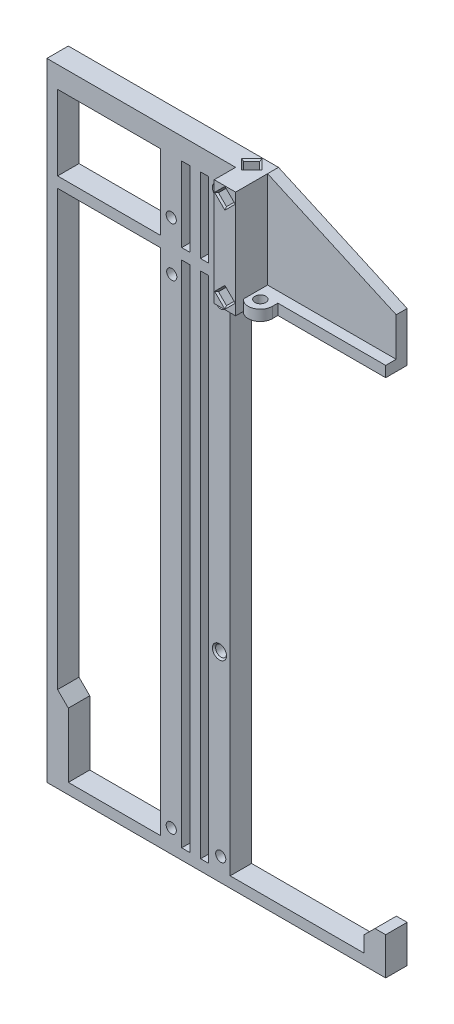
SolidWorks part; units mm, degrees
ref_plane "Front Plane" through (0, 0, 0) normal (0, 0, 1) x (1, 0, 0)
ref_plane "Top Plane" through (0, 0, 0) normal (0, 1, 0) x (1, 0, 0)
ref_plane "Right Plane" through (0, 0, 0) normal (1, 0, 0) x (0, 0, -1)
sketch "matx screw pattern" plane through (0, 0, 0) normal (0, 0, 1) x (1, 0, 0)
  line L1 (-121.92, 121.92) -> (121.92, 121.92) construction
  line L2 (-121.92, 121.92) -> (-121.92, -121.92) construction
  line L3 (-121.92, -121.92) -> (121.92, -121.92) construction
  line L4 (121.92, 121.92) -> (121.92, -121.92) construction
  point P4 (0, 121.92)
  point P6 (121.92, 0)
  point P7 (-111.76, -87.63)
  point P8 (-111.76, -41.91)
  point P9 (-88.9, 115.57)
  point P10 (43.18, -41.91)
  point P11 (43.18, -87.63)
  point P12 (43.18, -107.95)
  point P13 (115.57, -41.91)
  point P14 (115.57, 115.57)
  point P15 (43.18, 115.57)
  dimension "D1" = 243.84
  dimension "D2" = 10.16
  dimension "D3" = 22.86
  dimension "D4" = 227.33
  dimension "D5" = 154.94
  dimension "D6" = 203.2
  dimension "D7" = 45.72
  dimension "D8" = 20.32
  dimension "D9" = 34.29
sketch "Sketch1" plane through (0, 0, 0) normal (0, 0, 1) x (1, 0, 0)
  line L11 (47.4133, 127) -> (130.429, 127)
  line L12 (119.8033, 118.5333) -> (119.8033, 88.9)
  line L13 (181.229, -120.65) -> (47.4133, -120.65)
  line L14 (55.88, -116.4167) -> (55.88, -120.65) construction
  line L15 (55.88, -116.4167) -> (55.88, -91.0167)
  line L16 (51.6467, 118.5333) -> (92.1956, 118.5333)
  line L17 (51.6467, 118.5333) -> (51.6467, 88.9)
  line L18 (55.88, -116.4167) -> (92.1956, -116.4167)
  line L19 (111.3367, 118.5333) -> (111.3367, 88.9)
  line L20 (55.88, -91.0167) -> (51.6467, -86.7833)
  line L21 (119.8033, 118.5333) -> (121.9623, 118.5333)
  line L22 (121.9623, 118.5333) -> (121.9623, 88.9)
  line L26 (130.429, 127) -> (130.429, 88.9)
  line L27 (119.8033, -116.4167) -> (172.7623, -116.4167)
  line L29 (55.88, -116.4167) -> (47.4133, -116.4167) construction
  line L30 (47.4133, -120.65) -> (47.4133, 127)
  line L31 (172.7623, -116.4167) -> (172.7623, -110.0667)
  line L32 (172.7623, -110.0667) -> (176.9957, -105.8333)
  line L33 (92.1956, 118.5333) -> (92.1956, 88.9)
  line L34 (51.6467, 84.6667) -> (92.1956, 84.6667)
  line L35 (100.6623, -116.4167) -> (103.8828, -116.4167)
  line L36 (100.6623, 118.5333) -> (100.6623, 88.9)
  line L37 (100.6623, 118.5333) -> (103.8828, 118.5333)
  line L38 (100.6623, 84.6667) -> (103.8828, 84.6667)
  line L40 (119.8033, 84.6667) -> (181.229, 84.6667)
  line L41 (51.6467, 88.9) -> (92.1956, 88.9)
  line L42 (100.6623, 88.9) -> (103.8828, 88.9)
  line L43 (119.8033, 88.9) -> (121.9623, 88.9)
  line L44 (130.429, 88.9) -> (181.229, 88.9)
  line L45 (92.1956, -116.4167) -> (100.6623, -116.4167) construction
  line L46 (51.6467, 84.6667) -> (51.6467, -86.7833)
  line L47 (92.1956, 84.6667) -> (92.1956, -116.4167)
  line L48 (100.6623, 84.6667) -> (100.6623, -116.4167)
  line L49 (111.3367, 84.6667) -> (111.3367, -116.4167)
  line L50 (119.8033, 84.6667) -> (119.8033, -116.4167)
  line L54 (111.3367, -116.4167) -> (119.8033, -116.4167) construction
  line L55 (51.6467, 118.5333) -> (51.6467, 127) construction
  line L56 (172.7623, -116.4167) -> (181.229, -116.4167) construction
  line L57 (51.6467, -86.7833) -> (47.4133, -86.7833) construction
  line L58 (176.9957, -105.8333) -> (181.229, -105.8333)
  line L59 (51.6467, 88.9) -> (51.6467, 84.6667) construction
  line L60 (-121.92, 121.92) -> (121.92, 121.92) construction
  line L61 (121.9623, 88.9) -> (130.429, 88.9) construction
  line L62 (181.229, -105.8333) -> (181.229, -120.65)
  line L63 (103.8828, 118.5333) -> (103.8828, 88.9)
  line L64 (108.1161, 118.5333) -> (108.1161, 88.9)
  line L65 (108.1161, -116.4167) -> (111.3367, -116.4167)
  line L66 (108.1161, 88.9) -> (111.3367, 88.9)
  line L67 (108.1161, 84.6667) -> (111.3367, 84.6667)
  line L68 (103.8828, 84.6667) -> (103.8828, -116.4167)
  line L69 (108.1161, 84.6667) -> (108.1161, -116.4167)
  line L70 (108.1161, 118.5333) -> (111.3367, 118.5333)
  line L71 (103.8828, -116.4167) -> (108.1161, -116.4167) construction
  line L72 (181.229, 88.9) -> (181.229, 84.6667)
  point P0 (115.57, -116.4167)
  dimension "D2" = 4.2333
  dimension "D3" = 38.1
  dimension "D4" = 8.4667
  dimension "D5" = 4.2333
  dimension "D6" = 5.08
  dimension "D7" = 6.35
  dimension "D8" = 25.4
  dimension "D9" = 50.8
  dimension "D10" = 45
  dimension "D11" = 247.65
  dimension "D12" = 133.8157
  dimension "D13" = 40.549
extrude "Boss-Extrude1" add sketch "Sketch1" against normal blind 8.4667 from offset 9.525 offset against normal yes
sketch "Sketch9" plane through (0, 0, -17.9917) normal (0, 0, 1) x (1, 0, 0)
  line L3 (181.229, 88.9) -> (130.429, 88.9)
  line L4 (130.429, 127) -> (130.429, 88.9)
  line L7 (130.429, 127) -> (181.229, 104.14)
  line L9 (181.229, 104.14) -> (181.229, 88.9)
  dimension "D1" = 38.1
  dimension "D2" = 15.24
extrude "Boss-Extrude2" add sketch "Sketch9" along normal blind 4.318
sketch "Sketch16" plane through (0, 0, -9.525) normal (0, 0, 1) x (1, 0, 0)
  line L0 (119.8033, 84.6667) -> (181.229, 84.6667) construction
  line L1 (130.429, 127) -> (121.9623, 127)
  line L2 (130.429, 127) -> (130.429, 84.6667)
  line L3 (130.429, 84.6667) -> (121.9623, 84.6667)
  line L4 (121.9623, 127) -> (121.9623, 84.6667)
  line L5 (121.9623, 88.9) -> (121.9623, 118.5333) construction
extrude "Boss-Extrude3" add sketch "Sketch16" along normal blind 8.4667
sketch "Sketch18" plane through (0, 84.6667, 0) normal (0, -1, 0) x (-1, 0, 0)
  line L0 (-138.6515, 7.3467) -> (-138.6515, 9.525)
  line L1 (-47.4133, 9.525) -> (-181.229, 9.525) construction
  line L2 (-129.1265, 7.3467) -> (-129.1265, 9.525)
  line L3 (-138.6515, 9.525) -> (-129.1265, 9.525)
  arc A0 (-138.6515, 7.3467) -> (-129.1265, 7.3467) centre (-133.889, 7.3467) ccw
  point P1 (-133.889, 7.3467)
  point P8 (-133.889, 7.3467)
  dimension "D1" = 9.525
extrude "Boss-Extrude4" add sketch "Sketch18" against normal up to surface (4.2333 mm away) up to face at (155.829, 88.9, -11.5993)
sketch "Sketch21" plane through (0, 88.9, 0) normal (0, 1, 0) x (1, 0, 0)
  arc A0 (130.429, 4.0741) -> (138.6515, 7.3467) centre (133.889, 7.3467) ccw construction
  point P0 (133.889, 7.3467)
hole_wizard "#18 (0.1695) Diameter Hole3" positions "Sketch21" profile "Sketch22" hole size "#18" standard "ANSI Inch" end condition up to next
sketch "Sketch22" plane through (133.889, 88.9, -7.3467) normal (1, 0, 0) x (0, 0, 1)
  line L0 (0, 0) -> (0, 4.2333)
  line L1 (0, 4.2333) -> (2.1526, 4.2333)
  line L2 (2.1526, 4.2333) -> (2.1526, 0)
  line L5 (2.1526, 0) -> (0, 0)
  line L11 (0, -6.35) -> (0, 107.95) construction
  dimension "Thru Hole Dia." = 4.3053
  dimension "Thru Hole Depth" = 4.2333
sketch "Sketch5" plane through (0, 0, -9.525) normal (0, 0, 1) x (1, 0, 0)
  point P15 (115.57, 115.57)
  point P18 (115.57, -41.91)
hole_wizard "#18 (0.1695) Diameter Hole1" positions "Sketch5" profile "Sketch6" hole size "#18" standard "ANSI Inch" end condition through all
sketch "Sketch6" plane through (115.57, 115.57, -9.525) normal (1, 0, 0) x (0, -1, 0)
  line L0 (0, 0) -> (0, 8.4667)
  line L1 (0, 8.4667) -> (2.1526, 8.4667)
  line L2 (2.1526, 8.4667) -> (2.1526, 0.635)
  line L3 (2.1526, 0.635) -> (2.7876, 0)
  line L5 (2.7876, 0) -> (0, 0)
  line L6 (-2.1526, 0.635) -> (-2.7876, 0) construction
  line L11 (0, -6.35) -> (0, 107.95) construction
  dimension "Thru Hole Dia." = 4.3053
  dimension "Thru Hole Depth" = 8.4667
  dimension "Near C'Sink Dia." = 5.5753
  dimension "Near C'Sink Angle" = 90
sketch "Sketch2" plane through (0, -120.65, 0) normal (0, -1, 0) x (1, 0, 0)
  line L0 (173.8207, -13.7583) -> (176.9957, -10.5833)
  line L1 (173.8207, -13.7583) -> (176.9957, -16.9333)
  line L2 (176.9957, -10.5833) -> (180.1707, -13.7583)
  line L3 (176.9957, -16.9333) -> (180.1707, -13.7583)
  line L4 (173.8207, -13.7583) -> (180.1707, -13.7583) construction
  line L5 (176.9957, -10.5833) -> (176.9957, -16.9333) construction
  line L6 (48.4717, -13.7583) -> (51.6467, -10.5833)
  line L7 (48.4717, -13.7583) -> (51.6467, -16.9333)
  line L8 (51.6467, -10.5833) -> (54.8217, -13.7583)
  line L9 (51.6467, -16.9333) -> (54.8217, -13.7583)
  line L10 (48.4717, -13.7583) -> (54.8217, -13.7583) construction
  line L11 (51.6467, -10.5833) -> (51.6467, -16.9333) construction
  line L12 (47.4133, -17.9917) -> (47.4133, -9.525) construction
  line L14 (181.229, -17.9917) -> (181.229, -9.525) construction
  point P1 (176.9957, -13.7583)
  point P2 (51.6467, -13.7583)
  point P13 (47.4133, -13.7583)
  dimension "D1" = 6.35
  dimension "D2" = 4.2333
  dimension "D3" = 4.2333
extrude "bottom pins" cut sketch "Sketch2" against normal blind 6.35
sketch "Sketch3" plane through (47.4133, 0, 0) normal (-1, 0, 0) x (0, 0, 1)
  line L0 (-16.9333, 122.7667) -> (-13.7583, 125.9417)
  line L1 (-16.9333, 122.7667) -> (-13.7583, 119.5917)
  line L2 (-13.7583, 125.9417) -> (-10.5833, 122.7667)
  line L3 (-13.7583, 119.5917) -> (-10.5833, 122.7667)
  line L4 (-16.9333, 122.7667) -> (-10.5833, 122.7667) construction
  line L5 (-13.7583, 125.9417) -> (-13.7583, 119.5917) construction
  line L10 (-17.9917, 127) -> (-9.525, 127) construction
  line L11 (-17.9917, -120.65) -> (-9.525, -120.65) construction
  line L12 (-16.9333, -97.79) -> (-13.7583, -94.615)
  line L15 (-16.9333, -97.79) -> (-13.7583, -100.965)
  line L16 (-13.7583, -94.615) -> (-10.5833, -97.79)
  line L17 (-13.7583, -100.965) -> (-10.5833, -97.79)
  line L18 (-16.9333, -97.79) -> (-10.5833, -97.79) construction
  line L19 (-13.7583, -94.615) -> (-13.7583, -100.965) construction
  point P1 (-13.7583, 122.7667)
  point P9 (-13.7583, -97.79)
  point P18 (-13.7583, -120.65)
  dimension "D1" = 6.35
  dimension "D2" = 4.2333
  dimension "D3" = 22.86
extrude "rear pins" cut sketch "Sketch3" against normal blind 6.35
sketch "Sketch8" plane through (0, 0, -1.0583) normal (0, 0, 1) x (1, 0, 0)
  line L0 (123.0207, 88.9) -> (126.1957, 92.075)
  line L1 (123.0207, 88.9) -> (126.1957, 85.725)
  line L2 (126.1957, 92.075) -> (129.3707, 88.9)
  line L3 (126.1957, 85.725) -> (129.3707, 88.9)
  line L4 (123.0207, 88.9) -> (129.3707, 88.9) construction
  line L5 (126.1957, 92.075) -> (126.1957, 85.725) construction
  line L7 (121.9623, 88.9) -> (121.9623, 84.6667) construction
  line L9 (123.0207, 122.7667) -> (126.1957, 125.9417)
  line L10 (123.0207, 122.7667) -> (126.1957, 119.5917)
  line L11 (126.1957, 125.9417) -> (129.3707, 122.7667)
  line L12 (126.1957, 119.5917) -> (129.3707, 122.7667)
  line L13 (123.0207, 122.7667) -> (129.3707, 122.7667) construction
  line L14 (126.1957, 125.9417) -> (126.1957, 119.5917) construction
  line L15 (130.429, 127) -> (121.9623, 127) construction
  line L16 (119.8033, 84.6667) -> (121.9623, 84.6667) construction
  point P1 (126.1957, 88.9)
  point P10 (126.1957, 122.7667)
  dimension "D1" = 6.35
  dimension "D2" = 4.2333
  dimension "D3" = 4.2333
  dimension "D4" = 4.2333
extrude "left pins" cut sketch "Sketch8" against normal blind 6.35
sketch "Sketch24" plane through (0, 127, 0) normal (0, 1, 0) x (1, 0, 0)
  line L0 (120.904, 13.7583) -> (124.079, 16.9333)
  line L1 (120.904, 13.7583) -> (124.079, 10.5833)
  line L2 (124.079, 16.9333) -> (127.254, 13.7583)
  line L3 (124.079, 10.5833) -> (127.254, 13.7583)
  line L4 (120.904, 13.7583) -> (127.254, 13.7583) construction
  line L5 (124.079, 16.9333) -> (124.079, 10.5833) construction
  line L6 (130.429, 13.6737) -> (130.429, 1.0583) construction
  line L7 (130.429, 17.9917) -> (47.4133, 17.9917) construction
  line L8 (120.904, 13.7583) -> (124.079, 13.7583) construction
  point P1 (124.079, 13.7583)
  dimension "D1" = 6.35
  dimension "D2" = 6.35
  dimension "D3" = 4.2333
extrude "Cut-Extrude3" cut sketch "Sketch24" against normal blind 6.35
chamfer "Chamfer2" distance 0.635 angle 45 56 edges at (50.0592, -114.3, -12.1708) (53.2342, -114.3, -12.1708) (53.2342, -114.3, -15.3458) (50.0592, -114.3, -15.3458) (175.4082, -114.3, -12.1708) (178.5832, -114.3, -12.1708) (178.5832, -114.3, -15.3458) (175.4082, -114.3, -15.3458) (53.7633, -96.2025, -15.3458) (53.7633, -96.2025, -12.1708) (53.7633, -99.3775, -12.1708) (53.7633, -99.3775, -15.3458) (50.0592, -120.65, -12.1708) (50.0592, -120.65, -15.3458) (53.2342, -120.65, -15.3458) (53.2342, -120.65, -12.1708) (175.4082, -120.65, -15.3458) (175.4082, -120.65, -12.1708) (178.5832, -120.65, -12.1708) (178.5832, -120.65, -15.3458) (47.4133, -99.3775, -15.3458) (47.4133, -99.3775, -12.1708) (47.4133, -96.2025, -12.1708) (47.4133, -96.2025, -15.3458) (47.4133, 124.3542, -12.1708) (47.4133, 124.3542, -15.3458) (47.4133, 121.1792, -15.3458) (47.4133, 121.1792, -12.1708) (53.7633, 124.3542, -15.3458) (53.7633, 124.3542, -12.1708) (53.7633, 121.1792, -12.1708) (53.7633, 121.1792, -15.3458) (124.6082, 90.4875, -7.4083) (127.7832, 90.4875, -7.4083) (127.7832, 87.3125, -7.4083) (124.6082, 87.3125, -7.4083) (127.7832, 87.3125, -1.0583) (124.6082, 87.3125, -1.0583) (124.6082, 90.4875, -1.0583) (127.7832, 90.4875, -1.0583) (124.6082, 124.3542, -7.4083) (127.7832, 124.3542, -7.4083) (127.7832, 121.1792, -7.4083) (124.6082, 121.1792, -7.4083) (127.7832, 121.1792, -1.0583) (124.6082, 121.1792, -1.0583) (124.6082, 124.3542, -1.0583) (127.7832, 124.3542, -1.0583) (122.4915, 120.65, -15.3458) (125.6665, 120.65, -15.3458) (125.6665, 120.65, -12.1708) (122.4915, 120.65, -12.1708) (125.6665, 127, -15.3458) (125.6665, 127, -12.1708) (122.4915, 127, -12.1708) (122.4915, 127, -15.3458)
sketch "Sketch14" plane through (0, 0, -17.9917) normal (0, 0, -1) x (-1, 0, 0)
  point P0 (-116.078, 97.155)
  point P1 (-96.528, 97.155)
  point P3 (-96.728, 77.805)
  point P5 (-116.078, 77.605)
  point P7 (-116.078, -111.625)
  point P9 (-96.528, -111.625)
hole_wizard "#18 (0.1695) Diameter Hole2" positions "Sketch14" profile "Sketch15" hole size "#18" standard "ANSI Inch"
sketch "Sketch15" plane through (116.078, 97.155, -17.9917) normal (1, 0, 0) x (0, 1, 0)
  line L0 (0, 0) -> (0, 9.6754)
  line L1 (0, 9.6754) -> (2.1526, 8.382)
  line L2 (2.1526, 8.382) -> (2.1526, 0.635)
  line L3 (2.1526, 0.635) -> (2.7876, 0)
  line L5 (2.7876, 0) -> (0, 0)
  line L6 (-2.1526, 0.635) -> (-2.7876, 0) construction
  line L10 (0, 9.6754) -> (-2.1526, 8.382) construction
  line L11 (0, -6.35) -> (0, 107.95) construction
  dimension "Hole Dia." = 4.3053
  dimension "Hole Depth" = 8.382
  dimension "Near C'Sink Dia." = 5.5753
  dimension "Near C'Sink Angle" = 90
  dimension "Drill Angle" = 118
